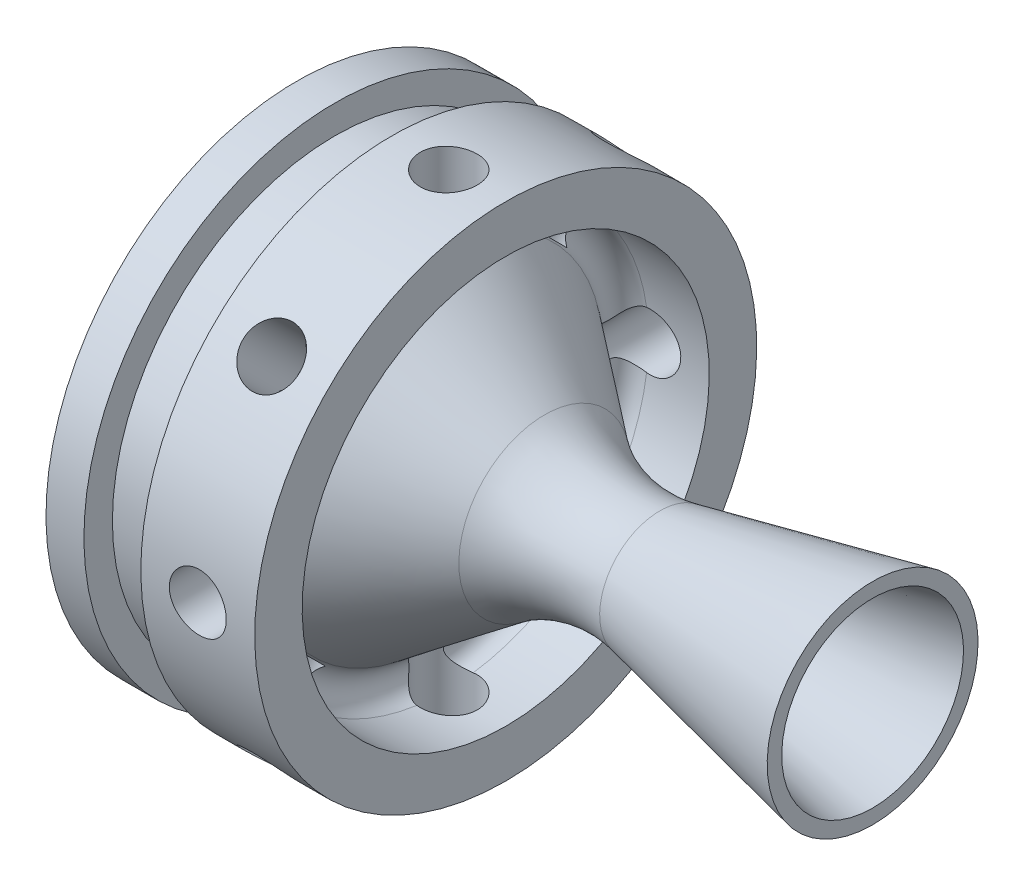
SolidWorks part; units mm, degrees
material "Plain Carbon Steel"
ref_plane "Front Plane" through (0, 0, 0) normal (0, 0, 1) x (1, 0, 0)
ref_plane "Top Plane" through (0, 0, 0) normal (0, 1, 0) x (1, 0, 0)
ref_plane "Right Plane" through (0, 0, 0) normal (1, 0, 0) x (0, 0, -1)
sketch "Sketch1" plane through (0, 0, 0) normal (0, 0, 1) x (1, 0, 0)
  line L0 (-30.4472, 0) -> (30.2153, 0) construction
  line L1 (-8.4472, 26.5) -> (-30.4472, 26.5) construction
  line L2 (1.0396, 3.3764) -> (30.2153, 9.5778)
  line L3 (30.2153, 9.5778) -> (30.2153, 11.1114)
  line L4 (0, 0) -> (0, 26.45) construction
  line L6 (-20.4472, 26.45) -> (-8.4472, 26.45)
  line L9 (-3.0091, 4.2739) -> (-30.4472, 24.95)
  line L10 (-48.4934, 26.45) -> (-22.3285, 26.45) construction
  line L11 (-30.4472, 24.95) -> (-30.4472, 26.45)
  line L12 (-30.4472, 26.45) -> (-26.4472, 26.45)
  line L14 (-8.4472, 26.45) -> (-8.4472, 21.45)
  line L16 (-26.4472, 26.45) -> (-26.4472, 23.45)
  line L17 (-26.4472, 23.45) -> (-20.4472, 23.45)
  line L18 (-20.4472, 26.45) -> (-20.4472, 23.45)
  line L19 (-16.0438, 17.8527) -> (-4.3478, 9.0391)
  line L20 (7.7981, 6.3464) -> (30.2153, 11.1114)
  line L21 (-8.4472, 21.45) -> (-14.8402, 21.45)
  arc A0 (-14.8402, 21.45) -> (-16.0438, 17.8527) centre (-14.8402, 19.45) ccw
  arc A1 (-4.3478, 9.0391) -> (7.7981, 6.3464) centre (4.6794, 21.0187) ccw
  arc A2 (-3.0091, 4.2739) -> (1.0396, 3.3764) centre (0, 8.2671) ccw
  point P11 (0, 3.2671)
  dimension "D14" = 37
  dimension "D15" = 1.5
  dimension "D16" = 2
  dimension "D10" = 15
  dimension "D6" = 5
  dimension "D3" = 3
  dimension "D5" = 12
  dimension "D8" = 5
  dimension "D9" = 1.5
  dimension "D12" = 6
  dimension "D13" = 3
  dimension "D18" = 4
  dimension "Throat" = 3.2671
  dimension "Exit" = 9.5778
  dimension "Clearance" = 0.05
  dimension "ID" = 26.5
  dimension "Shoulder" = 22
revolve "Revolve1" add sketch "Sketch1" angle 360 about L0
fillet "Fillet1" [suppressed] radius 5
fillet "Fillet2" [suppressed] radius 3
ref_axis "Axis1" through (-38.9811, 0, 0) along (1, 0, 0)
ref_plane "Plane1" through (0, 18, 0) normal (0, 1, 0) x (-1, 0, 0)
sketch "Sketch4" plane through (0, 18, 0) normal (0, 1, 0) x (-1, 0, 0)
  line L0 (38.9811, 0) -> (-52.3884, 0) construction
  line L1 (8.4472, 26.45) -> (20.4472, 26.45) construction
  circle A0 centre (14.4472, 0) radius 3
  point P9 (14.4472, 26.45)
  dimension "Diameter" = 6
extrude "Cut-Extrude2" cut sketch "Sketch4" along normal blind 80
pattern_circular "CirPattern2" count 8 over 360 about axis through (-38.9811, 0, 0) along (1, 0, 0) of "Cut-Extrude2"
